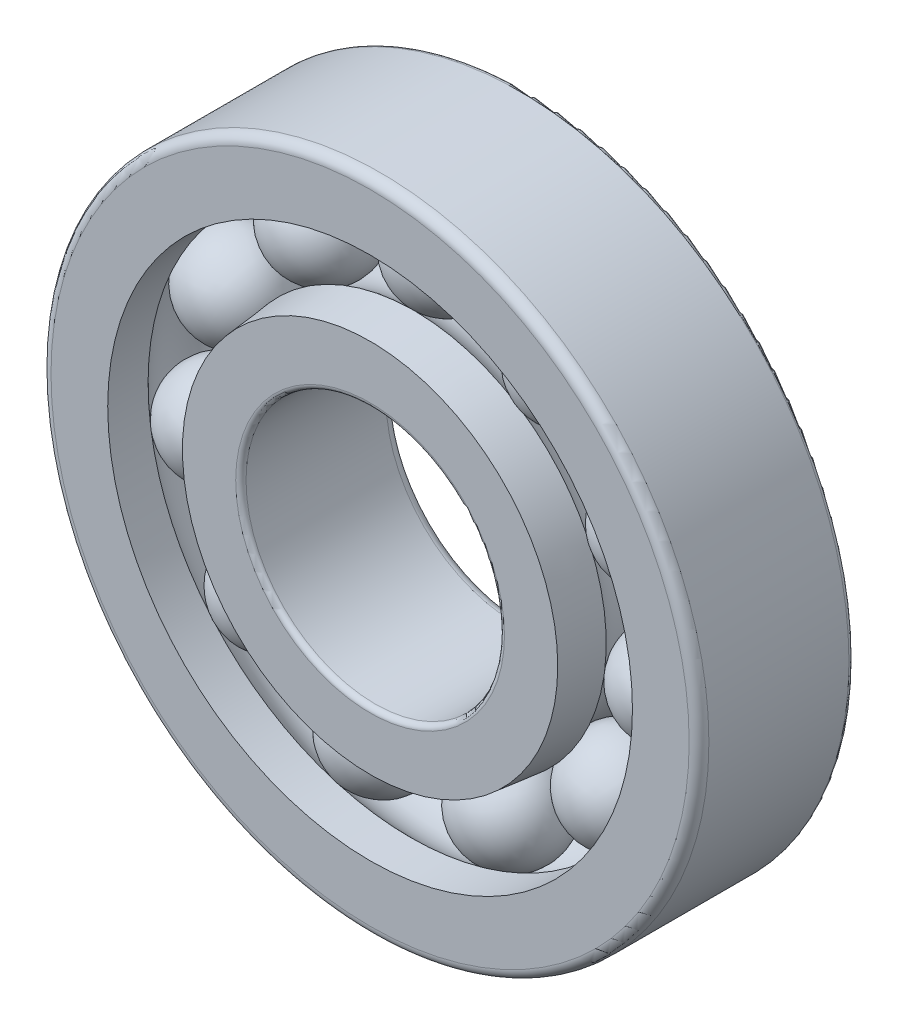
SolidWorks part; units mm, degrees
ref_plane "Front Plane" through (0, 0, 0) normal (0, 0, 1) x (1, 0, 0)
ref_plane "Top Plane" through (0, 0, 0) normal (0, 1, 0) x (1, 0, 0)
ref_plane "Right Plane" through (0, 0, 0) normal (1, 0, 0) x (0, 0, -1)
sketch "BaseSke" plane through (0, 0, 0) normal (1, 0, 0) x (0, 0, -1)
  line L0 (-47.2296, 0) -> (24.6132, 0) construction
  line L1 (-47.2296, 48.75) -> (24.6132, 48.75) construction
  line L2 (0, 129.5214) -> (0, -86.3012) construction
  line L3 (0, 59.375) -> (0, 38.125)
  line L4 (-16.5, 70) -> (16.5, 70) construction
  line L5 (-16.5, 27.5) -> (16.5, 27.5) construction
  arc A0 (0, 59.375) -> (0, 38.125) centre (0, 48.75) ccw
  dimension "Ball_diameter" = 21.25
  dimension "D1" = 48.75
revolve "Ball" add sketch "BaseSke" angle 360 about L3
sketch "OuterRaceSke" plane through (0, 0, 0) normal (1, 0, 0) x (0, 0, -1)
  line L0 (0, 0) -> (0, 87.5396) construction
  line L1 (-16.5, 70) -> (16.5, 70)
  line L2 (-16.5, 70) -> (-16.5, 55.8333)
  line L3 (-16.5, 55.8333) -> (-7.906, 55.8333)
  line L4 (16.5, 70) -> (16.5, 57.5676)
  line L5 (-50.3916, 0) -> (55.2197, 0) construction
  line L6 (-47.2296, 48.75) -> (24.6132, 48.75) construction
  line L8 (16.5, 57.5676) -> (7.1607, 56.586)
  line L9 (0, 55.8333) -> (-0.8658, 59.0647) construction
  line L10 (0, 55.8333) -> (7.1607, 56.586) construction
  arc A0 (7.1607, 56.586) -> (-7.906, 55.8333) centre (0, 48.75) ccw
  dimension "D4" = 21.23
  dimension "D2" = 111.6667
  dimension "D3" = 6
revolve "OuterRace" add sketch "OuterRaceSke" angle 360 about L5
sketch "InnerRaceSke" plane through (0, 0, 0) normal (1, 0, 0) x (0, 0, -1)
  line L0 (-70.8626, 0) -> (113.5527, 0) construction
  line L1 (0, 58.441) -> (0, -70.8113) construction
  line L2 (-16.5, 27.5) -> (16.5, 27.5)
  line L3 (-16.5, 27.5) -> (-16.5, 41.6667)
  line L4 (-16.5, 41.6667) -> (-7.906, 41.6667)
  line L5 (16.5, 27.5) -> (16.5, 41.6667)
  line L6 (0, 129.5214) -> (0, -86.3012) construction
  line L7 (7.906, 41.6667) -> (16.5, 41.6667)
  arc A0 (-7.906, 41.6667) -> (7.906, 41.6667) centre (0, 48.75) ccw
  arc A1 (0, 59.375) -> (0, 38.125) centre (0, 48.75) ccw construction
  dimension "D2" = 21.23
  dimension "D1" = 83.3333
revolve "InnerRace" add sketch "InnerRaceSke" angle 360 about L0
fillet "Fillet1" radius 2.1 2 edges at (27.5, 0, -16.5) (70, 0, 16.5)
fillet "Fillet2" radius 1.1 2 edges at (70, 0, -16.5) (27.5, 0, 16.5)
sketch "CutInnerRaceSke" plane through (0, 0, 0) normal (1, 0, 0) x (0, 0, -1)
  line L0 (-7.906, 41.6667) -> (-16.5, 41.6667)
  line L1 (-16.5, 41.6667) -> (-16.5, 39.9324)
  line L2 (-16.5, 39.9324) -> (-7.1607, 40.914)
  line L3 (-7.1607, 40.914) -> (0, 41.6667) construction
  line L4 (0, 58.441) -> (0, -70.8113) construction
  line L5 (-28.3066, 0) -> (35.2466, 0) construction
  arc A0 (-7.906, 41.6667) -> (-7.1607, 40.914) centre (0, 48.75) ccw
  arc A1 (-7.906, 41.6667) -> (7.906, 41.6667) centre (0, 48.75) ccw construction
  dimension "D1" = 6
revolve "CutInnerRace" cut sketch "CutInnerRaceSke" angle 360 about L5
pattern_circular "CirPatternBall" count 11 over 360 about axis through (0, 0, 50.3916) along (0, 0, -1) of "Ball"
sketch "SimplifiedSke" plane through (0, 0, 0) normal (1, 0, 0) x (0, 0, -1)
  line L0 (37.5911, 0) -> (-37.5911, 0) construction
  circle A0 centre (0, 48.75) radius 10.625
  arc A1 (0, 59.375) -> (0, 38.125) centre (0, 48.75) ccw construction
revolve "Simplified" [suppressed] add sketch "SimplifiedSke" angle 360 about L0
equation "\"D1@BaseSke\" =  (\"Bearing_Outside_Diameter@BaseSke\"  +  \"Bearing_Inside_Diameter@BaseSke\"  )  / 4"
equation "\"Ball_diameter@BaseSke\" =  ( \"Bearing_Outside_Diameter@BaseSke\" - \"Bearing_Inside_Diameter@BaseSke\" ) / 4 "
equation "\"D2@OuterRaceSke\" = \"Bearing_Outside_Diameter@BaseSke\" -  ( \"Bearing_Outside_Diameter@BaseSke\" - \"Bearing_Inside_Diameter@BaseSke\" )  / 3"
equation "\"D4@OuterRaceSke\" = (  \"Bearing_Outside_Diameter@BaseSke\" - \"Bearing_Inside_Diameter@BaseSke\" ) / 4 -0.02"
equation "\"D3@OuterRaceSke\" = \"Angle@OuterRaceSke\"/2.5"
equation "\"D1@InnerRaceSke\" = \"Bearing_Inside_Diameter@BaseSke\" +  ( \"Bearing_Outside_Diameter@BaseSke\" - \"Bearing_Inside_Diameter@BaseSke\" )  / 3"
equation "\"D2@InnerRaceSke\" = \"D4@OuterRaceSke\""
equation "\"D1@CirPatternBall\" = int( \"D1@BaseSke\"* pi  * 2 / \"Ball_diameter@BaseSke\"/1.2 ) -1"
equation "\"D1@CutInnerRaceSke\" = \"D3@OuterRaceSke\""
